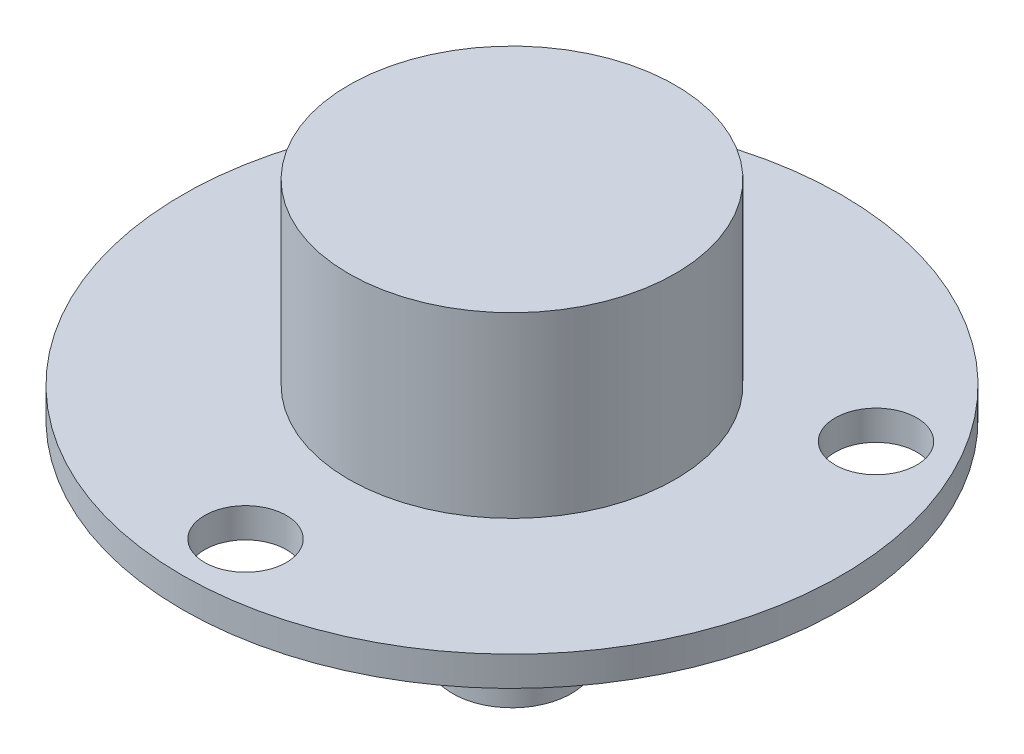
SolidWorks part; units mm, degrees
material "ABS"
ref_plane "Front Plane" through (0, 0, 0) normal (0, 0, 1) x (1, 0, 0)
ref_plane "Top Plane" through (0, 0, 0) normal (0, 1, 0) x (1, 0, 0)
ref_plane "Right Plane" through (0, 0, 0) normal (1, 0, 0) x (0, 0, -1)
sketch "Sketch1" plane through (0, 0, 0) normal (0, 1, 0) x (1, 0, 0)
  circle A0 centre (0, 0) radius 22.2
  dimension "D1" = 44.4
extrude "Boss-Extrude1" add sketch "Sketch1" along normal blind 2
sketch "Sketch2" plane through (0, 2, 0) normal (0, 1, 0) x (1, 0, 0)
  circle A0 centre (0, 0) radius 11
  dimension "D1" = 22
extrude "Boss-Extrude2" add sketch "Sketch2" along normal blind 12
extrude "Boss-Extrude3" add sketch "Sketch2<2>" against normal blind 7
sketch "Sketch2<2>" plane through (0, 2, 0) normal (0, 1, 0) x (1, 0, 0) same geometry as "Sketch2"
sketch "Sketch3" plane through (0, -5, 0) normal (0, -1, 0) x (1, 0, 0)
  circle A0 centre (0, 0) radius 4
  dimension "D1" = 8
extrude "Boss-Extrude4" add sketch "Sketch3" along normal blind 9
sketch "Sketch4" plane through (0, 2, 0) normal (0, 1, 0) x (1, 0, 0)
  circle A0 centre (0, -17.95) radius 2.75
  circle A2 centre (-15.5452, 8.975) radius 2.75
  circle A3 centre (15.5452, 8.975) radius 2.75
  point P9 (0, 0)
  dimension "D1" = 5.5
  dimension "D2" = 17.95
  dimension "D3" = 3
extrude "Cut-Extrude1" cut sketch "Sketch4" against normal blind 3.1
